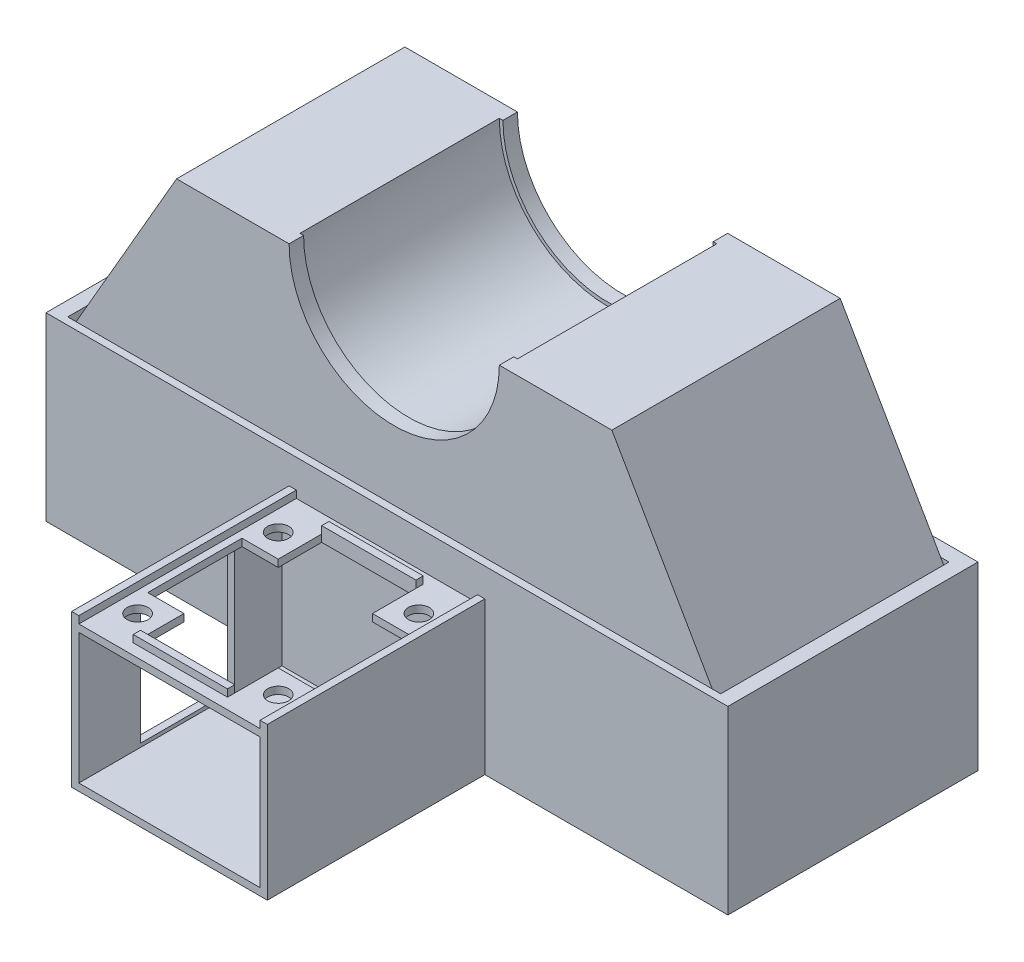
SolidWorks part; units mm, degrees
ref_plane "Front Plane" through (0, 0, 0) normal (0, 0, 1) x (1, 0, 0)
ref_plane "Top Plane" through (0, 0, 0) normal (0, 1, 0) x (1, 0, 0)
ref_plane "Right Plane" through (0, 0, 0) normal (1, 0, 0) x (0, 0, -1)
sketch "Frame" plane through (0, 0, 0) normal (0, 0, 1) x (1, 0, 0)
  line L0 (15, 0) -> (18, 0) construction
  line L1 (0, 0) -> (0, -26) construction
  line L2 (45.0333, -26) -> (0, 52)
  line L3 (0, 52) -> (-45.0333, -26)
  line L4 (-45.0333, -26) -> (45.0333, -26)
  line L5 (0, 0) -> (-30.0222, 0)
  line L6 (0, 0) -> (30.0222, 0)
  circle A0 centre (0, 0) radius 15
  circle A1 centre (0, 0) radius 18
  point P6 (0, 0)
  dimension "D1" = 30
  dimension "D2" = 3
  dimension "D3" = 26
extrude "Boss-Extrude1" add sketch "Frame" along normal blind 27.5 contours A1 L5 L3 L4 L2 L6 | L5 A1 L6 A0 region at (0, -25.0626, 0) region at (0, -17.5975, 0)
sketch "lip" plane through (0, 0, 27.5) normal (0, 0, 1) x (1, 0, 0)
  line L0 (-14.5, 0) -> (-30.0222, 0)
  line L1 (-30.0222, 0) -> (-45.0333, -26)
  line L2 (-45.0333, -26) -> (45.0333, -26)
  line L3 (45.0333, -26) -> (30.0222, 0)
  line L4 (30.0222, 0) -> (14.5, 0)
  circle A0 centre (0, 0) radius 14.5
  circle A1 centre (0, 0) radius 15
  line M1 (30.0222, 0) -> (15, 0)
  arc M2 (15, 0) -> (-15, 0) centre (0, 0) cw
  line M3 (-15, 0) -> (-30.0222, 0)
  line M4 (-30.0222, 0) -> (-45.0333, -26)
  line M5 (-45.0333, -26) -> (45.0333, -26)
  line M6 (45.0333, -26) -> (30.0222, 0)
  dimension "D1" = 30
  dimension "D2" = 0.5
extrude "Boss-Extrude2" add sketch "lip" along normal blind 2 contours M6 M1 M2 M3 M4 M5 | A0 L0 L4 M2 region at (0, -14.8354, 27.5) region at (0, -15.5255, 27.5)
sketch "lip2" plane through (0, 0, 0) normal (0, 0, -1) x (-1, 0, 0)
  line L0 (-15, 0) -> (-30.0222, 0)
  line L1 (-30.0222, 0) -> (-45.0333, -26)
  line L2 (-45.0333, -26) -> (-30.0222, 0) construction
  line L3 (45.0333, -26) -> (-45.0333, -26) construction
  line L4 (-45.0333, -26) -> (45.0333, -26)
  line L5 (45.0333, -26) -> (30.0222, 0)
  line L6 (30.0222, 0) -> (15, 0)
  line L7 (-15, 0) -> (-14.5, 0)
  line L8 (15, 0) -> (14.5, 0)
  circle A0 centre (0, 0) radius 15
  circle A1 centre (0, 0) radius 14.5
  line M1 (-15, 0) -> (-30.0222, 0)
  line M2 (-30.0222, 0) -> (-45.0333, -26)
  line M3 (-45.0333, -26) -> (45.0333, -26)
  line M4 (45.0333, -26) -> (30.0222, 0)
  line M5 (30.0222, 0) -> (15, 0)
  arc M6 (15, 0) -> (-15, 0) centre (0, 0) cw
  dimension "D1" = 30
  dimension "D2" = 0.5
extrude "Boss-Extrude3" add sketch "lip2" along normal blind 2 contours M6 M1 M2 M3 M4 M5 | A1 L7 L8 M6 region at (0, -15.5255, 0) region at (14.75, -0.3354, 0)
sketch "Encoder Rail" plane through (0, 0, 29.5) normal (0, 0, 1) x (1, 0, 0)
  line L0 (0, -24) -> (0, -26) construction
  line L1 (-45.0333, -26) -> (45.0333, -26) construction
  line L2 (-45.0333, -26) -> (45.0333, -26)
  line L3 (-45.0333, -48.92) -> (45.0333, -48.92)
  line L4 (45.0333, -48.92) -> (45.0333, -26)
  line L5 (-45.0333, -48.92) -> (-45.0333, -26)
  line L6 (0, -24) -> (0, -24.7)
  line L7 (0, -24.7) -> (0, -28.92)
  line L8 (-12.5, -28.92) -> (12.5, -28.92)
  line L9 (12.5, -28.92) -> (12.5, -48.92)
  line L10 (12.5, -48.92) -> (-12.5, -48.92)
  line L11 (-12.5, -48.92) -> (-12.5, -28.92)
  line L12 (12.5, -28.92) -> (12.5, -48.92)
  line L13 (12.5, -28.92) -> (13.5, -28.92)
  line L14 (12.5, -48.92) -> (13.5, -48.92)
  line L15 (13.5, -28.92) -> (13.5, -48.92)
  line L16 (-12.5, -28.92) -> (-12.5, -48.92)
  line L17 (-12.5, -28.92) -> (-13.5, -28.92)
  line L18 (-12.5, -48.92) -> (-13.5, -48.92)
  line L19 (-13.5, -28.92) -> (-13.5, -48.92)
  line L20 (-13.5, -28.92) -> (-12.5, -28.92)
  line L21 (-13.5, -28.92) -> (-13.5, -27.92)
  line L22 (-12.5, -28.92) -> (-12.5, -27.92)
  line L23 (-13.5, -27.92) -> (-12.5, -27.92)
  line L24 (12.5, -28.92) -> (13.5, -28.92)
  line L25 (12.5, -28.92) -> (12.5, -27.92)
  line L26 (13.5, -28.92) -> (13.5, -27.92)
  line L27 (12.5, -27.92) -> (13.5, -27.92)
  line L28 (47.0333, -48.92) -> (-47.0333, -48.92)
  line L29 (-12.5, -28.92) -> (-11.5, -28.92)
  line L30 (-12.5, -28.92) -> (-12.5, -29.92)
  line L31 (-12.5, -29.92) -> (-11.5, -29.92)
  line L32 (-11.5, -28.92) -> (-11.5, -29.92)
  line L33 (12.5, -28.92) -> (11.5, -28.92)
  line L34 (12.5, -28.92) -> (12.5, -29.92)
  line L35 (12.5, -29.92) -> (11.5, -29.92)
  line L36 (11.5, -28.92) -> (11.5, -29.92)
  line L37 (47.0333, -48.92) -> (47.0333, -24)
  line L38 (-47.0333, -48.92) -> (-47.0333, -24)
  line L39 (47.0333, -24) -> (-47.0333, -24)
  line L40 (45.0333, -26) -> (45.0333, -24)
  line L41 (-45.0333, -26) -> (-45.0333, -24)
  line L42 (-11.5, -29.92) -> (11.5, -29.92)
  line L43 (0, -28.92) -> (0, -38.92) construction
  line L44 (-2, -40.92) -> (2, -40.92)
  line L45 (-2, -40.92) -> (-2, -36.92)
  line L46 (-2, -36.92) -> (2, -36.92)
  line L47 (2, -40.92) -> (2, -36.92)
  line L48 (-2, -40.92) -> (2, -36.92) construction
  line L49 (-2, -36.92) -> (2, -40.92) construction
  line L50 (0, -38.92) -> (0, -48.92) construction
  line L51 (0, -38.92) -> (-12.5, -38.92) construction
  line L52 (-12.5, -38.92) -> (12.5, -38.92) construction
  circle A0 centre (0, 0) radius 24
  point P20 (0, -28.92)
  point P34 (-11.5, -29.42)
  point P41 (0, -38.92)
  line M7 (-45.0333, -26) -> (45.0333, -26)
  dimension "D1" = 48
  dimension "D2" = 2
  dimension "D3" = 22.92
  dimension "D4" = 0.7
  dimension "D5" = 4.22
  dimension "D6" = 20
  dimension "D7" = 25
  dimension "D8" = 1
  dimension "D9" = 1
  dimension "D10" = 2
  dimension "D11" = 2
  dimension "D12" = 2
  dimension "D13" = 1
  dimension "D14" = 1
  dimension "D15" = 2
extrude "Boss-Extrude6" add sketch "Encoder Rail" against normal through all separate body contours L23 L21 L17 L22 | L17 L19 L3 L11 L16 | L27 L25 L13 L26 | L15 L13 L9 L12 L3 | L8 L36 L35 L9 | L36 L8 L32 L31 L11 L3 L12 L35 | L32 L8 L16 L31 | L21 L23 L22 L8 L7 L5 L3 L19 M7 | L25 L27 L26 L15 L3 L4 L2 L7 L8 | L40 L4 L28 L37 L39 | L5 L41 L39 L38 L28 region at (-28.1219, -36.954, 29.5) region at (-46.0333, -36.46, 29.5) region at (28.1219, -36.954, 29.5) region at (46.0333, -36.46, 29.5) region at (-13, -38.92, 29.5) region at (-12, -29.42, 29.5) region at (12, -29.42, 29.5) region at (-12.186, -39.42, 29.5) region at (-13, -28.42, 29.5) region at (13, -38.92, 29.5) region at (13, -28.42, 29.5)
sketch "Sketch3" plane through (0, 0, -2) normal (0, 0, -1) x (-1, 0, 0)
  line L1 (-47.0333, -24) -> (47.0333, -24)
  line L2 (-47.0333, -24) -> (-47.0333, -48.92)
  line L3 (-47.0333, -48.92) -> (47.0333, -48.92)
  line L4 (47.0333, -24) -> (47.0333, -48.92)
extrude "Boss-Extrude7" add sketch "Sketch3" along normal blind 2
sketch "Sketch4" plane through (0, 0, 29.5) normal (0, 0, 1) x (1, 0, 0)
  line L1 (-47.0333, -24) -> (47.0333, -24)
  line L2 (-47.0333, -24) -> (-47.0333, -48.92)
  line L3 (-47.0333, -48.92) -> (47.0333, -48.92)
  line L4 (47.0333, -24) -> (47.0333, -48.92)
extrude "Boss-Extrude8" add sketch "Sketch4" along normal blind 1
sketch "Sketch6" plane through (0, -48.92, 0) normal (0, -1, 0) x (-1, 0, 0)
  line L1 (45.0333, -28.5) -> (-45.0333, -28.5)
  line L2 (45.0333, -28.5) -> (45.0333, 2)
  line L3 (45.0333, 2) -> (-45.0333, 2)
  line L4 (-45.0333, -28.5) -> (-45.0333, 2)
  dimension "D1" = 2
  dimension "D2" = 2
  dimension "D3" = 2
  dimension "D4" = 2
extrude "Cut-Extrude1" cut sketch "Sketch6" against normal offset from surface (17.92 mm away) 5
extrude "Boss-Extrude10" add sketch "Encoder Rail<9>" along normal blind 2 from offset 1 separate body contours L15 L13 L9 L12 L3 | L42 L31 L11 L3 L12 L35 L47 L44 L45 L46 | L44 L47 L46 L45 | L17 L19 L3 L11 L16 | L23 L21 L17 L22 | L32 L8 L16 L31 | L32 L42 L36 L8 | L8 L36 L35 L9 | L27 L25 L13 L26 region at (0, -29.42, 29.5) region at (-13, -38.92, 29.5) region at (-12, -29.42, 29.5) region at (12, -29.42, 29.5) region at (-12.186, -39.42, 29.5) region at (-13, -28.42, 29.5) region at (13, -38.92, 29.5) region at (13, -28.42, 29.5) region at (0, -38.92, 29.5)
sketch "Encoder Rail<9>" plane through (0, 0, 29.5) normal (0, 0, 1) x (1, 0, 0) same geometry as "Encoder Rail"
extrude "Cut-Extrude2" cut sketch "Encoder Rail<10>" along normal blind 1 contours L44 L47 L46 L45 region at (0, -38.92, 29.5)
sketch "Encoder Rail<10>" plane through (0, 0, 29.5) normal (0, 0, 1) x (1, 0, 0) same geometry as "Encoder Rail"
extrude "Boss-Extrude11" add sketch "Encoder Rail<11>" along normal blind 1 contours L44 L47 L46 L45
sketch "Encoder Rail<11>" plane through (0, 0, 29.5) normal (0, 0, 1) x (1, 0, 0) same geometry as "Encoder Rail"
sketch "Sketch8" plane through (0, 0, 32.5) normal (0, 0, 1) x (1, 0, 0)
  line L1 (-13.5, -27.92) -> (-12.5, -27.92)
  line L2 (-13.5, -27.92) -> (-13.5, -48.92)
  line L3 (-13.5, -48.92) -> (-12.5, -48.92)
  line L4 (-12.5, -27.92) -> (-12.5, -48.92)
  line L5 (13.5, -27.92) -> (12.5, -27.92)
  line L6 (13.5, -27.92) -> (13.5, -48.92)
  line L7 (13.5, -48.92) -> (12.5, -48.92)
  line L8 (12.5, -27.92) -> (12.5, -48.92)
  line L9 (-12.5, -28.92) -> (12.5, -28.92)
  line L10 (-12.5, -28.92) -> (-12.5, -29.92)
  line L11 (-12.5, -29.92) -> (12.5, -29.92)
  line L12 (12.5, -28.92) -> (12.5, -29.92)
  line L13 (-13.5, -48.92) -> (13.5, -48.92)
  line L14 (-13.5, -48.92) -> (-13.5, -47.92)
  line L15 (-13.5, -47.92) -> (13.5, -47.92)
  line L16 (13.5, -48.92) -> (13.5, -47.92)
  line M1 (12.5, -28.92) -> (-12.5, -28.92)
  line M2 (-12.5, -28.92) -> (-12.5, -27.92)
  line M3 (-12.5, -27.92) -> (-13.5, -27.92)
  line M4 (-13.5, -27.92) -> (-13.5, -48.92)
  line M5 (-13.5, -48.92) -> (13.5, -48.92)
  line M6 (13.5, -48.92) -> (13.5, -27.92)
  line M7 (13.5, -27.92) -> (12.5, -27.92)
  line M8 (12.5, -27.92) -> (12.5, -28.92)
  dimension "D1" = 1
extrude "Boss-Extrude12" add sketch "Sketch8" along normal blind 28 contours L4 M2 M3 M4 M5 | L4 L11 L8 M1 | L8 M8 M5 M6 M7 | L15 L2 L4 M5 | L15 L4 L8 M5 | L15 L8 M5 M6 region at (-13, -37.92, 32.5) region at (-13, -48.42, 32.5) region at (0, -29.42, 32.5) region at (0, -48.42, 32.5) region at (13, -37.92, 32.5) region at (13, -48.42, 32.5)
sketch "Sketch9" plane through (0, -28.92, 0) normal (0, 1, 0) x (1, 0, 0)
  line L0 (-11.5, -39) -> (-11.5, -52)
  line L1 (-12.5, -33) -> (12.5, -33)
  line L2 (-12.5, -33) -> (-12.5, -58)
  line L3 (-12.5, -58) -> (12.5, -58)
  line L4 (12.5, -33) -> (12.5, -58)
  line L5 (12.5, -60.5) -> (12.5, -30.5) construction
  line L6 (-12.5, -30.5) -> (12.5, -30.5) construction
  line L7 (11.5, -39) -> (11.5, -52)
  line L8 (12.5, -58) -> (6.5, -58)
  line L9 (12.5, -58) -> (12.5, -52)
  line L10 (12.5, -52) -> (6.5, -52)
  line L11 (6.5, -58) -> (6.5, -52)
  line L12 (12.5, -33) -> (6.5, -33)
  line L13 (12.5, -33) -> (12.5, -39)
  line L14 (12.5, -39) -> (6.5, -39)
  line L15 (6.5, -33) -> (6.5, -39)
  line L16 (-12.5, -33) -> (-6.5, -33)
  line L17 (-12.5, -33) -> (-12.5, -39)
  line L18 (-12.5, -39) -> (-6.5, -39)
  line L19 (-6.5, -33) -> (-6.5, -39)
  line L20 (-12.5, -58) -> (-6.5, -58)
  line L21 (-12.5, -58) -> (-12.5, -52)
  line L22 (-12.5, -52) -> (-6.5, -52)
  line L23 (-6.5, -58) -> (-6.5, -52)
  line L24 (6.5, -57) -> (-6.5, -57)
  line L25 (-6.5, -34) -> (6.5, -34)
  line L26 (-6.5, -58) -> (6.5, -58)
  line L27 (-6.5, -58) -> (-6.5, -59)
  line L28 (6.5, -58) -> (6.5, -59)
  line L29 (-6.5, -59) -> (6.5, -59)
  line L30 (6.5, -33) -> (-6.5, -33)
  line L31 (6.5, -33) -> (6.5, -32)
  line L32 (-6.5, -33) -> (-6.5, -32)
  line L33 (6.5, -32) -> (-6.5, -32)
  circle A0 centre (-9.7, -55.2) radius 1.45
  circle A1 centre (9.7, -55.2) radius 1.45
  circle A2 centre (9.7, -35.8) radius 1.45
  circle A3 centre (-9.7, -35.8) radius 1.45
  point P36 (11.5, -45.5)
  dimension "D6" = 2.9
  dimension "D1" = 2.5
  dimension "D2" = 25
  dimension "D3" = 6
  dimension "D4" = 2.8
  dimension "D5" = 2.8
  dimension "D7" = 2.8
  dimension "D8" = 2.8
  dimension "D9" = 1
  dimension "D10" = 1
  dimension "D11" = 1
  dimension "D12" = 1
  dimension "D13" = 1
  dimension "D14" = 1
extrude "Cut-Extrude4" cut sketch "Sketch9" against normal up to surface (1 mm away) contours L25 L19 L18 L0 L22 L23 L24 L11 L10 L7 L14 L15 | A1 | A0 | A3 | A2 | L11 L24 L23 L3 | L19 L25 L15 L1 region at (0, -28.92, 45.5) region at (0, -28.92, 33.5) region at (0, -28.92, 57.5) region at (-9.7, -28.92, 55.2) region at (9.7, -28.92, 55.2) region at (9.7, -28.92, 35.8) region at (-9.7, -28.92, 35.8) up to face at (0, -29.92, 46.5)
extrude "Boss-Extrude13" add sketch "Sketch9<4>" along normal blind 1 contours L31 L33 L32 L1 | L27 L29 L28 L3 region at (0, -28.92, 32.5) region at (0, -28.92, 58.5)
sketch "Sketch9<4>" plane through (0, -28.92, 0) normal (0, 1, 0) x (1, 0, 0) same geometry as "Sketch9"
sketch "Sketch11" plane through (-13.5, 0, 0) normal (-1, 0, 0) x (0, 0, 1)
  line L0 (52, -30.42) -> (39, -30.42)
  line L1 (52, -30.42) -> (52, -47.42)
  line L2 (39, -30.42) -> (39, -47.42)
  line L3 (52, -47.42) -> (39, -47.42)
  line L4 (60.5, -27.92) -> (30.5, -27.92) construction
  line L5 (60.5, -48.92) -> (30.5, -48.92) construction
  line L6 (52, -28.92) -> (52, -48.92) construction
  line L7 (58, -28.92) -> (52, -28.92) construction
  line L8 (39, -28.92) -> (39, -48.92) construction
  line L9 (33, -28.92) -> (39, -28.92) construction
  line L10 (39, -28.92) -> (52, -28.92) construction
  dimension "D1" = 2.5
  dimension "D2" = 1.5
extrude "Cut-Extrude5" cut sketch "Sketch11" against normal up to surface (1 mm away) up to face at (-12.5, -38.92, 46.5)
equation "\"1mmm\"=8"
